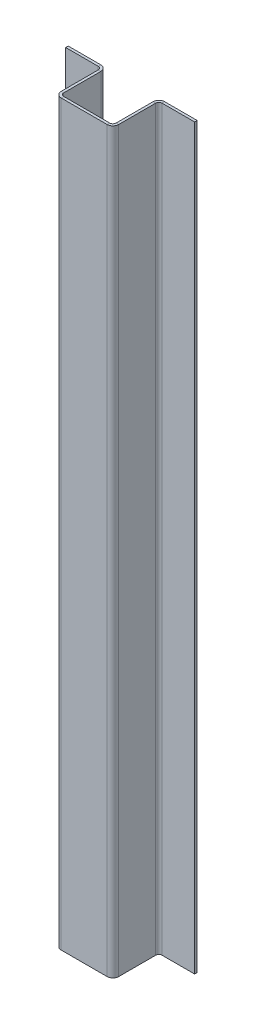
SolidWorks part; units mm, degrees
note: The reader was unsure of these and kept them because the rebuilt part matched: flange length of "Edge-Flange1", "Edge-Flange2".
material "Galvanized Steel"
ref_plane "Front Plane" through (0, 0, 0) normal (0, 0, 1) x (1, 0, 0)
ref_plane "Top Plane" through (0, 0, 0) normal (0, 1, 0) x (1, 0, 0)
ref_plane "Right Plane" through (0, 0, 0) normal (1, 0, 0) x (0, 0, -1)
sketch "Sketch1" plane through (0, 0, 0) normal (0, 0, 1) x (1, 0, 0)
  line L1 (22.5, -289) -> (-22.5, -289)
  line L2 (22.5, -289) -> (22.5, 289)
  line L3 (22.5, 289) -> (-22.5, 289)
  line L4 (-22.5, -289) -> (-22.5, 289)
  line L5 (22.5, -289) -> (-22.5, 289) construction
  line L6 (22.5, 289) -> (-22.5, -289) construction
  point P0 (0, 0)
  dimension "D1" = 578
  dimension "D2" = 45
base flange "Base-Flange1" sketch "Sketch1" thickness 2 reverse thickness direction no parameters "D1"=8
edge flange "Edge-Flange1" sketch "Sketch10" flange profiles "Sketch10", "Sketch11" flange angle 90 flange length 38 flange position material inside bend radius 2.5 thickness 2 relief rectangular parameters "D6"=10, "D8"=1
sketch "Sketch10" plane through (22.5, 0, -2) normal (1, 0, 0) x (0, -1, 0)
  line L0 (289, 0) -> (-289, 0) construction
  line L1 (289, 0) -> (-289, 0)
  line L2 (-289, 0) -> (-289, 36)
  line L3 (-289, 36) -> (289, 36)
  line L4 (289, 36) -> (289, 0)
sketch "Sketch11" plane through (-22.5, 0, -2) normal (-1, 0, 0) x (0, 1, 0)
  line L0 (289, 0) -> (-289, 0) construction
  line L1 (289, 0) -> (-289, 0)
  line L2 (-289, 0) -> (-289, 36)
  line L3 (-289, 36) -> (289, 36)
  line L4 (289, 36) -> (289, 0)
bend "EdgeBend1" bend radius 2.5 bend angle 90 parameters "D5"=1
bend "EdgeBend2" bend radius 2.5 bend angle 90 parameters "D5"=2
edge flange "Edge-Flange2" sketch "Sketch16" flange profiles "Sketch16", "Sketch17" flange angle 90 flange length 30 flange position material inside bend radius 2.5 thickness 2 relief rectangular parameters "D6"=10, "D8"=1
sketch "Sketch16" plane through (-22.5, 0, -38) normal (0, 0, -1) x (0, -1, 0)
  line L2 (-289, 0) -> (-289, 28)
  line L3 (-289, 28) -> (289, 28)
  line L4 (289, 28) -> (289, 0)
  line L7 (-289, 0) -> (289, 0) construction
  line L8 (-289, 0) -> (289, 0)
sketch "Sketch17" plane through (22.5, 0, -38) normal (0, 0, -1) x (0, 1, 0)
  line L0 (-289, 0) -> (289, 0) construction
  line L1 (-289, 0) -> (289, 0)
  line L2 (-289, 0) -> (-289, 28)
  line L3 (-289, 28) -> (289, 28)
  line L4 (289, 28) -> (289, 0)
bend "EdgeBend3" bend radius 2.5 bend angle 90 parameters "D5"=3
bend "EdgeBend4" bend radius 2.5 bend angle 90 parameters "D5"=4
sketch "Bend-Lines1" [suppressed] plane through (0, 0, 0) normal (0, 1, 0) x (1, 0, 0)
sketch "Bounding-Box1" [suppressed] plane through (0, 0, 0) normal (0, 1, 0) x (1, 0, 0)
sheet metal parameters "Sheet-Metal8" thickness 2 parameters "D1"=8
flat pattern "Flat-Pattern8" [suppressed]
sketch "Bend-Lines2" plane through (0, 0, 0) normal (0, 1, 0) x (1, 0, 0)
sketch3d "Bounding-Box2" [suppressed]
  line L0 (-20, 1200, 0) -> (-20, -1200, 0) construction
  line L1 (20, 1200, 0) -> (20, -1200, 0) construction
  line L2 (-20, 1200, 0) -> (20, 1200, 0) construction
  line L3 (-20, -1200, 0) -> (20, -1200, 0) construction
sheet metal parameters "Sheet-Metal9" thickness 2 parameters "D1"=8
flat pattern "Flat-Pattern8"
sketch "Bend-Lines2" plane through (0, 0, 0) normal (0, 0, 1) x (1, 0, 0)
  line L0 (-18.2489, 1200) -> (-18.2489, -1200) construction
  line L1 (18.2489, -1200) -> (18.2489, 1200) construction
  line L2 (-18.2489, 1200) -> (-18.2489, -1200) construction
  line L3 (18.2489, -1200) -> (18.2489, 1200) construction
sketch3d "Bounding-Box2" [suppressed]
  line L0 (56.4978, 1200, 0) -> (56.4978, -1200, 0) construction
  line L1 (-56.4978, 1200, 0) -> (-56.4978, -1200, 0) construction
  line L2 (56.4978, 1200, 0) -> (-56.4978, 1200, 0) construction
  line L3 (56.4978, -1200, 0) -> (-56.4978, -1200, 0) construction
bend of the flat pattern "Flatten-<EdgeBend1>1"
bend of the flat pattern "Flatten-<EdgeBend2>1"
sheet metal parameters "Sheet-Metal10" thickness 2 parameters "D1"=8
flat pattern "Flat-Pattern8"
sketch "Bend-Lines2" plane through (0, 0, 0) normal (0, 0, 1) x (1, 0, 0)
  line L0 (-20.7489, 289) -> (-20.7489, -289) construction
  line L1 (20.7489, -289) -> (20.7489, 289) construction
  line L2 (-20.7489, 289) -> (-20.7489, -289) construction
  line L3 (20.7489, -289) -> (20.7489, 289) construction
  line L4 (55.2467, -289) -> (55.2467, 289) construction
  line L5 (-55.2467, 289) -> (-55.2467, -289) construction
  line L6 (55.2467, -289) -> (55.2467, 289) construction
  line L7 (-55.2467, 289) -> (-55.2467, -289) construction
sketch3d "Bounding-Box2" [suppressed]
  line L0 (83.4956, 289, 0) -> (83.4956, -289, 0) construction
  line L1 (-83.4956, 289, 0) -> (-83.4956, -289, 0) construction
  line L2 (83.4956, 289, 0) -> (-83.4956, 289, 0) construction
  line L3 (83.4956, -289, 0) -> (-83.4956, -289, 0) construction
bend of the flat pattern "Flatten-<EdgeBend1>1"
bend of the flat pattern "Flatten-<EdgeBend2>1"
bend of the flat pattern "Flatten-<EdgeBend3>1"
bend of the flat pattern "Flatten-<EdgeBend4>1"
